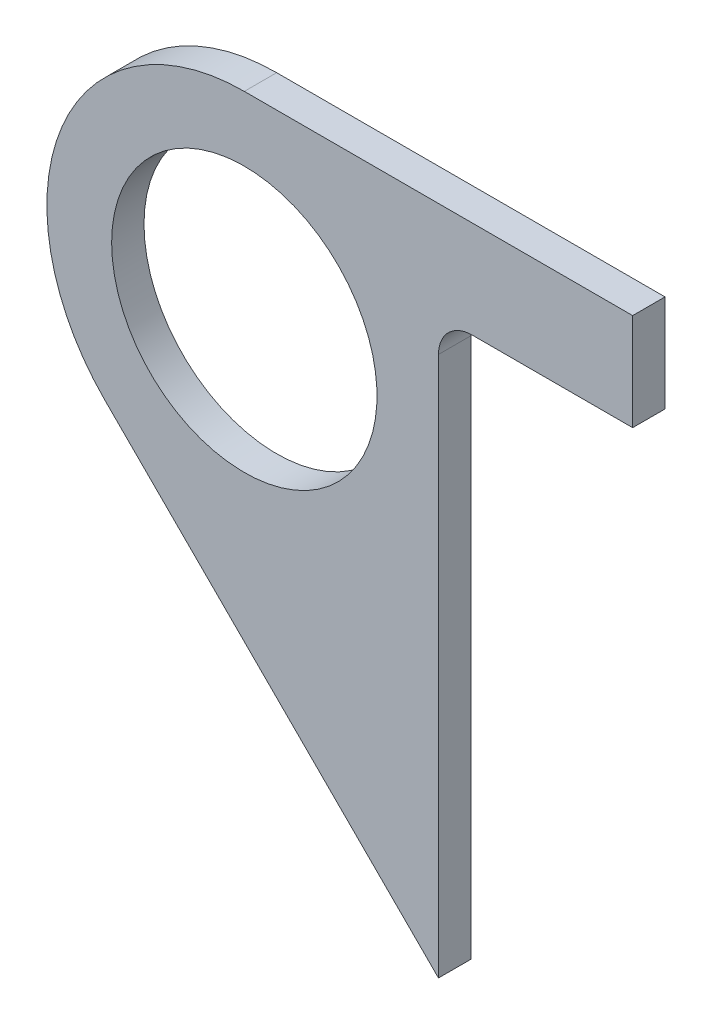
SolidWorks part; units mm, degrees
ref_plane "Front Plane" through (0, 0, 0) normal (0, 0, 1) x (1, 0, 0)
ref_plane "Top Plane" through (0, 0, 0) normal (0, 1, 0) x (1, 0, 0)
ref_plane "Right Plane" through (0, 0, 0) normal (1, 0, 0) x (0, 0, -1)
sketch "Sketch1" plane through (0, 0, 457.2) normal (0, 0, -1) x (-1, 0, 0)
  line L0 (273.05, 603.25) -> (273.05, 584.2)
  line L5 (273.05, 584.2) -> (311.15, 584.2)
  line L6 (311.15, 584.2) -> (311.15, 471.6354)
  line L8 (311.15, 471.6354) -> (376.6398, 537.1252)
  line L9 (273.05, 603.25) -> (349.25, 603.25)
  line L10 (311.15, 571.5) -> (311.15, 0) construction
  line L11 (-304.8, 603.25) -> (304.8, 603.25) construction
  arc A0 (349.25, 603.25) -> (376.6398, 537.1252) centre (349.25, 564.515) cw
  circle A1 centre (349.25, 564.515) radius 26.035
  dimension "D3" = 12.7
  dimension "D4" = 52.07
  dimension "D1" = 19.05
  dimension "D2" = 38.1
  dimension "D5" = 45
  dimension "D6" = 38.1
extrude "Boss-Extrude1" add sketch "Sketch1" along normal blind 6.35
fillet "Fillet1" radius 6.604 1 edges at (-311.15, 584.2, 454.025)
